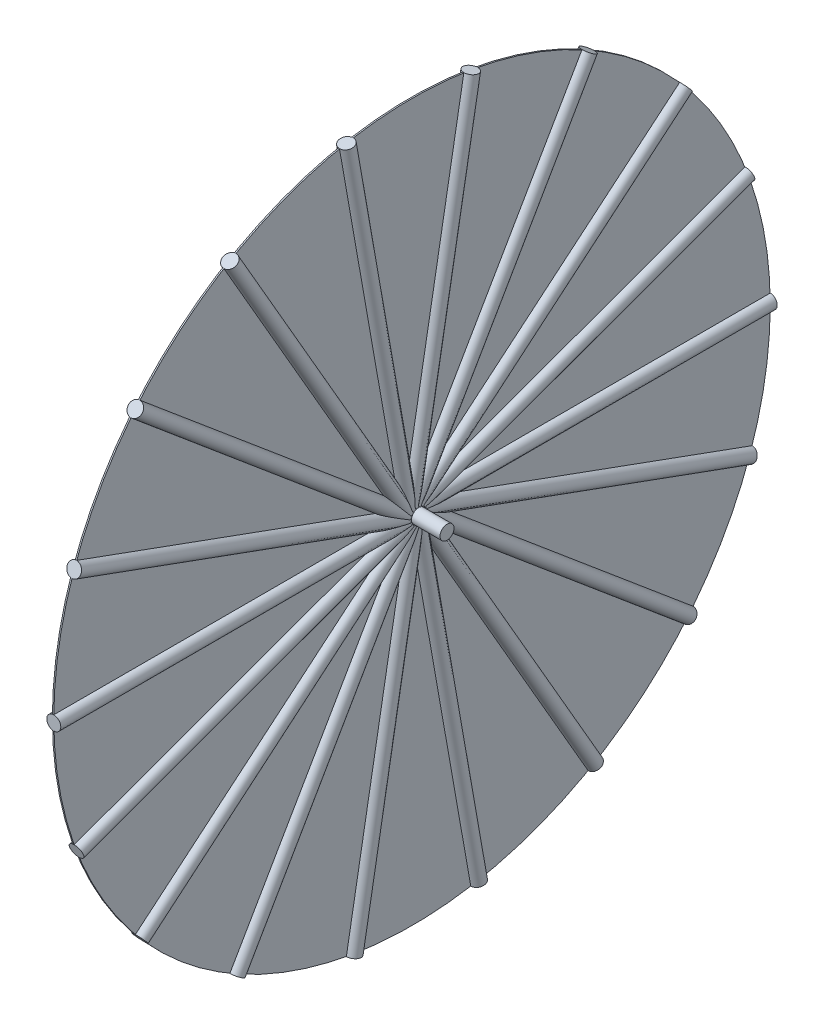
SolidWorks part; units mm, degrees
material "Glass"
ref_plane "Front Plane" through (0, 0, 0) normal (0, 0, 1) x (1, 0, 0)
ref_plane "Top Plane" through (0, 0, 0) normal (0, 1, 0) x (1, 0, 0)
ref_plane "Right Plane" through (0, 0, 0) normal (1, 0, 0) x (0, 0, -1)
sketch "Sketch3" plane through (39.7843, 0, 0) normal (0, 0, 1) x (1, 0, 0)
  line L1 (0, 0) -> (127.0469, 0)
  line L2 (0, 0) -> (0, 25.4)
  line L3 (0, 25.4) -> (127.0469, 25.4)
  line L4 (127.0469, 0) -> (127.0469, 25.4)
revolve "Revolve2" add sketch "Sketch3" angle 360 about L1
sketch "Sketch6" plane through (39.7843, 0, 0) normal (-1, 0, 0) x (0, 0, 1)
  line L1 (25.4, -12.7) -> (1300, -12.7)
  line L2 (25.4, -12.7) -> (25.4, 12.7)
  line L3 (25.4, 12.7) -> (1300, 12.7)
  line L4 (1300, -12.7) -> (1300, 12.7)
revolve "Revolve3" add sketch "Sketch6" angle 360 about L1
sketch "Sketch7" plane through (39.7843, 0, 0) normal (-1, 0, 0) x (0, 0, 1)
  circle A0 centre (0, 0) radius 1300
extrude "Boss-Extrude2" add sketch "Sketch7" along normal blind 5.08
pattern_circular "CirPattern1" count 18 over 360 about axis through (34.7043, 0, 0) along (-1, 0, 0) of "Revolve3"
